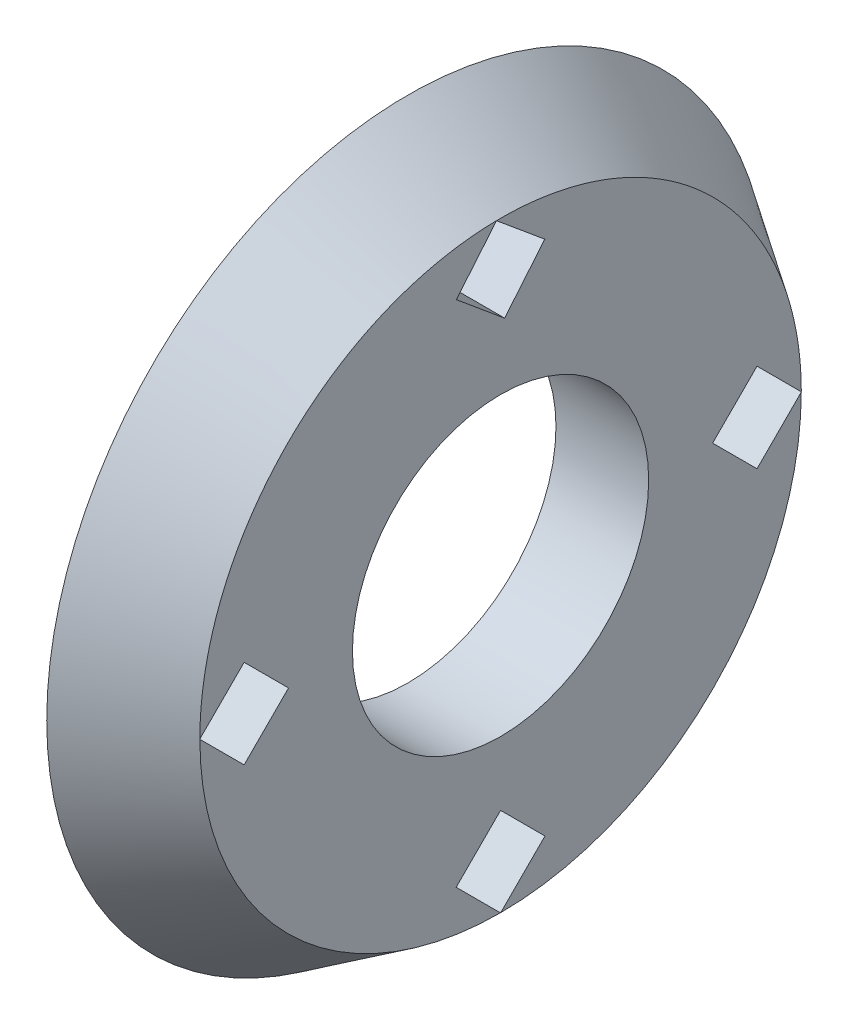
SolidWorks part; units mm, degrees
ref_plane "Front Plane" through (0, 0, 0) normal (0, 0, 1) x (1, 0, 0)
ref_plane "Top Plane" through (0, 0, 0) normal (0, 1, 0) x (1, 0, 0)
ref_plane "Right Plane" through (0, 0, 0) normal (1, 0, 0) x (0, 0, -1)
sketch "Sketch1" plane through (0, 0, 0) normal (0, 1, 0) x (1, 0, 0)
  circle A0 centre (0, 0) radius 26.5102
  dimension "D1" = 53.0205
extrude "Boss-Extrude1" add sketch "Sketch1" along normal blind 14.3784
sketch "Sketch2" plane through (0, 0, 0) normal (0, 0, 1) x (1, 0, 0)
  circle A0 centre (0, 7.1892) radius 21.1183
  dimension "D1" = 42.2366
  dimension "D2" = 7.1892
extrude "Boss-Extrude2" add sketch "Sketch2" along normal blind 25.4 and the other way blind 25.4
sketch "Sketch3" plane through (0, 0, 0) normal (1, 0, 0) x (0, 0, -1)
  circle A0 centre (0, 7.1892) radius 10.16
  dimension "D1" = 20.32
  dimension "D2" = 7.1892
extrude "Boss-Extrude3" add sketch "Sketch3" along normal blind 29.6555 and the other way blind 29.6555
sketch "Sketch5" plane through (0, 0, 0) normal (1, 0, 0) x (0, 0, -1)
  circle A0 centre (0, 7.1892) radius 7.1892
  circle A1 centre (0, 7.1892) radius 10.16 construction
  dimension "D1" = 14.3784
extrude "Cut-Extrude1" cut sketch "Sketch5" against normal through all and the other way through all
sketch "Sketch6" plane through (0, 0, 0) normal (0, 0, 1) x (1, 0, 0)
  circle A0 centre (0, 7.1892) radius 17.5237
  dimension "D1" = 35.0474
  dimension "D2" = 7.1892
extrude "Cut-Extrude2" cut sketch "Sketch6" against normal through all and the other way through all
sketch "Sketch7" plane through (0, 0, 0) normal (0, 1, 0) x (1, 0, 0)
  circle A0 centre (0, 0) radius 23.495
  dimension "D1" = 46.99
extrude "Cut-Extrude3" cut sketch "Sketch7" against normal through all and the other way through all
ref_plane "Plane1" through (-34.1555, 0, 0) normal (-1, 0, 0) x (0, 0, 1)
sketch "Sketch8" plane through (-34.1555, 0, 0) normal (-1, 0, 0) x (0, 0, 1)
  circle A0 centre (0, 7.1892) radius 17.526
  dimension "D1" = 35.052
sketch "Sketch9" plane through (-29.6555, 0, 0) normal (-1, 0, 0) x (0, 0, 1)
  circle A4 centre (0, 7.1892) radius 14.5938
  circle A5 centre (0, 7.1892) radius 7.1892 construction
  dimension "D1" = 29.1876
loft "Loft3" add profiles "Sketch9", "Sketch8" connector at (-29.6555, 11.9338, -13.8011) connector at (-34.1555, 12.6678, -16.6477)
extrude "Cut-Extrude4" cut sketch "Sketch5<2>" against normal through all
sketch "Sketch5<2>" plane through (0, 0, 0) normal (1, 0, 0) x (0, 0, -1) same geometry as "Sketch5"
sketch "Sketch12" plane through (-34.1555, 0, 0) normal (-1, 0, 0) x (0, 0, 1)
  line L1 (2.1462, 19.4377) -> (0.1975, 21.7814)
  line L2 (0.1975, 21.7814) -> (-2.1462, 19.8327)
  line L3 (-2.1462, 19.8327) -> (-0.1975, 17.489)
  line L4 (-0.1975, 17.489) -> (2.1462, 19.4377)
  line L5 (14.6013, 7.1892) -> (12.446, 9.3445)
  line L6 (12.446, 9.3445) -> (10.2907, 7.1892)
  line L7 (10.2907, 7.1892) -> (12.446, 5.034)
  line L8 (12.446, 5.034) -> (14.6013, 7.1892)
  line L9 (2.1553, -5.2568) -> (0, -3.1015)
  line L10 (0, -3.1015) -> (-2.1553, -5.2568)
  line L11 (-2.1553, -5.2568) -> (0, -7.412)
  line L12 (0, -7.412) -> (2.1553, -5.2568)
  line L13 (-10.2907, 7.1892) -> (-12.446, 9.3445)
  line L14 (-12.446, 9.3445) -> (-14.6013, 7.1892)
  line L15 (-14.6013, 7.1892) -> (-12.446, 5.034)
  line L16 (-12.446, 5.034) -> (-10.2907, 7.1892)
  circle A0 centre (0, 7.1892) radius 12.446 construction
  circle A1 centre (0, 19.6352) radius 1.524 construction
  circle A2 centre (12.446, 7.1892) radius 1.524 construction
  circle A3 centre (0, -5.2568) radius 1.524 construction
  circle A4 centre (-12.446, 7.1892) radius 1.524 construction
  dimension "D1" = 24.892
  dimension "D2" = 3.048
extrude "Cut-Extrude5" cut sketch "Sketch12" against normal up to surface (4.5 mm away) contours L15 L16 L13 L14 | L11 L12 L9 L10 | L7 L8 L5 L6 | L3 L4 L1 L2 region at (-34.1555, 7.1892, 12.446) region at (-34.1555, -5.2568, 0) region at (-34.1555, 7.1892, -12.446) up to face at (-29.6555, 7.1892, -10.16)
split "Split1" bodies to split 111 resulting bodies 112 split by face at (-29.6555, 3.4678, 0)
equation "\"D1@Boss-Extrude1\"=.16*3.538"
equation "\"D1@Sketch2\"=.47*3.538"
